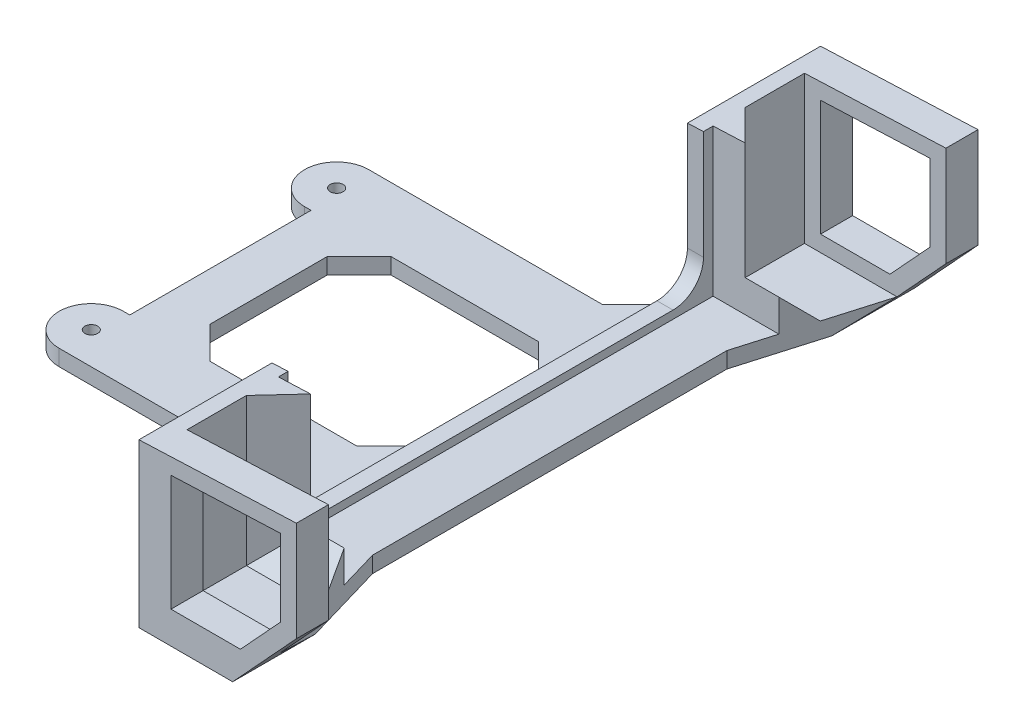
SolidWorks part; units mm, degrees
ref_plane "Front Plane" through (0, 0, 0) normal (0, 0, 1) x (1, 0, 0)
ref_plane "Top Plane" through (0, 0, 0) normal (0, 1, 0) x (1, 0, 0)
ref_plane "Right Plane" through (0, 0, 0) normal (1, 0, 0) x (0, 0, -1)
sketch "Sketch2" plane through (0, 0, 0) normal (0, 0, 1) x (1, 0, 0)
  line L2 (-5, -50.9445) -> (-5, -0.2052)
  line L4 (0, 0) -> (0, -45.9445)
  line L8 (44.0837, -29.3894) -> (44.0837, 1.809)
  line L9 (-5, -50.9445) -> (24.2279, -50.9445)
  line L13 (28.8337, -45.9445) -> (0, -45.9445)
  line L14 (44.0837, -29.3894) -> (24.2279, -50.9445)
  line L15 (44.0837, 1.809) -> (-5, -0.2052)
  dimension "D1" = 45.9445
  dimension "D2" = 2.35
  dimension "D3" = 28.8337
  dimension "D4" = 15.25
  dimension "D5" = 45
  dimension "D8" = 5
  dimension "D9" = 5
extrude "Boss-Extrude1" add sketch "Sketch2" along normal blind 10 contours L9 L14 L8 L15 L2
extrude "Boss-Extrude6" add sketch "Sketch2<5>" against normal blind 41 contours L13 L9 region at (-4.3884, -25.5748, 0)
sketch "Sketch2<5>" plane through (0, 0, 0) normal (0, 0, 1) x (1, 0, 0) same geometry as "Sketch2"
sketch "Sketch6" plane through (0, 0, 0) normal (1, 0, 0) x (0, 0, -1)
  line L0 (41, 0) -> (41, -45.9445) construction
  line L1 (41, -45.9445) -> (0, -45.9445) construction
  line L5 (41, -16.7445) -> (33, -16.7445) construction
  line L6 (33, 0) -> (33, -16.7445) construction
  line L8 (31.5, 0) -> (31.5, -33.9445)
  line L9 (31.5, 0) -> (41, 0)
  line L10 (41, 0) -> (41, -24.4445)
  line L11 (41, 0) -> (0, 0) construction
  circle A0 centre (41, -33.9445) radius 8 construction
  arc A1 (31.5, -33.9445) -> (41, -24.4445) centre (41, -33.9445) ccw
  circle A2 centre (41, -33.9445) radius 9.5 construction
  point P13 (41, -25.9445)
  point P15 (29.7596, -19.9849)
  point P16 (31.5, -33.9445)
  point P19 (0, 0)
  point P22 (33, 0)
  point P23 (41, -24.4445)
  dimension "D2" = 16
  dimension "D1" = 12
  dimension "D4" = 9.2
  dimension "D5" = 8
  dimension "Margin" = 1.5
extrude "Cut-Extrude1" cut sketch "Sketch6" against normal up to next
sketch "Sketch7" plane through (0, 0, 0) normal (0, 0, -1) x (-1, 0, 0)
  line L5 (-5, -4.799) -> (-39.0837, -3.4004)
  line L6 (-5, -4.799) -> (-39.0837, -3.4004)
  line L7 (-39.0837, -27.4374) -> (-26.6415, -40.9445)
  line L8 (-39.0837, -27.4374) -> (-26.6415, -40.9445)
  line L11 (-26.6415, -40.9445) -> (-5, -40.9445)
  line L12 (-5, -40.9445) -> (-5, -4.799)
  line L14 (-39.0837, -3.4004) -> (-39.0837, -27.4374)
  line L17 (-5, -40.9445) -> (-5, -4.799)
  line L19 (-39.0837, -3.4004) -> (-39.0837, -27.4374)
  line L22 (-26.6415, -40.9445) -> (-5, -40.9445)
  dimension "D1" = 5
extrude "Cut-Extrude2" cut sketch "Sketch7" against normal up to next
ref_plane "Plane1" through (0, 0, -28.5) normal (0, 0, 1) x (1, 0, 0)
sketch "Sketch10" plane through (0, 0, -28.5) normal (0, 0, 1) x (1, 0, 0)
  line L0 (28.8337, -45.9445) -> (0, -45.9445) construction
  line L1 (28.8337, -45.9445) -> (0, -45.9445)
  line L2 (0, 0) -> (0, -45.9445) construction
  line L3 (0, 0) -> (0, -45.9445)
  line L4 (28.8337, -45.9445) -> (28.8337, -35.9445)
  line L5 (28.8337, -35.9445) -> (10, -35.9445)
  line L6 (10, -35.9445) -> (10, 0.4103)
  line L7 (0, 0) -> (10, 0.4103)
  line L9 (44.0837, 1.809) -> (0, 0) construction
  dimension "D1" = 10
  dimension "D2" = 10
extrude "Boss-Extrude9" add sketch "Sketch10" along normal blind 10
chamfer "Chamfer3" distance 10 angle 45 2 edges at (19.4169, -35.9445, -18.5) (10, -17.7671, -18.5)
sketch "Sketch11" plane through (0, -45.9445, 0) normal (0, 1, 0) x (1, 0, 0)
  line L0 (28.8337, 41) -> (16.8337, 41)
  line L1 (28.8337, 41) -> (0, 41) construction
  line L2 (16.8337, 41) -> (28.8337, 0)
  line L3 (28.8337, 0) -> (28.8337, 41)
  dimension "D1" = 12
extrude "Cut-Extrude3" cut sketch "Sketch11" against normal through all both and the other way through all
ref_plane "Plane2" through (0, 0, -96.25) normal (0, 0, -1) x (-1, 0, 0)
sketch "Sketch12" plane through (0, 0, -41) normal (0, 0, -1) x (-1, 0, 0)
  line L6 (0, -45.9445) -> (-16.8337, -45.9445)
  line L7 (-16.8337, -45.9445) -> (-16.8337, -50.9445)
  line L8 (-16.8337, -50.9445) -> (5, -50.9445)
  line L9 (5, -50.9445) -> (5, -43.4445)
  line L10 (5, -43.4445) -> (0, -43.4445)
  line L11 (0, -43.4445) -> (0, -45.9445)
  line L12 (0, -45.9445) -> (-16.8337, -45.9445)
  line L13 (-16.8337, -45.9445) -> (-16.8337, -50.9445)
  line L14 (-16.8337, -50.9445) -> (5, -50.9445)
  line L15 (5, -50.9445) -> (5, -43.4445)
  line L16 (5, -43.4445) -> (0, -43.4445)
  line L17 (0, -43.4445) -> (0, -45.9445)
  dimension "D1" = 0
extrude "Boss-Extrude10" add sketch "Sketch12" along normal up to surface (55.25 mm away) up to plane "Plane2"
sketch "Sketch13" plane through (-5, 0, 0) normal (-1, 0, 0) x (0, 0, 1)
  line L0 (10, -50.9445) -> (-96.25, -50.9445) construction
  line L1 (-68, -50.9445) -> (-48, -50.9445)
  line L2 (-68, -50.9445) -> (-68, -45.9445)
  line L3 (-68, -45.9445) -> (-48, -45.9445)
  line L4 (-48, -50.9445) -> (-48, -45.9445)
  line L5 (-58, -45.9445) -> (-58, -50.9445) construction
  line L6 (-96.25, 11.2707) -> (-96.25, -11.2707) construction
  dimension "D1" = 5
  dimension "D2" = 20
  dimension "D3" = 38.25
extrude "Boss-Extrude11" add sketch "Sketch13" along normal blind 92.85
sketch "Sketch14" plane through (0, -45.9445, 0) normal (0, 1, 0) x (1, 0, 0)
  line L0 (-5, 58) -> (-97.85, 58) construction
  line L1 (-5, 48) -> (-5, 68) construction
  line L2 (-97.85, 48) -> (-97.85, 68) construction
  circle A0 centre (-87.85, 58) radius 2
  point P8 (-83.9374, 64)
  dimension "D1" = 10
  dimension "D2" = 4
extrude "Cut-Extrude4" cut sketch "Sketch14" against normal up to next
sketch "Sketch15" plane through (0, 0, -68) normal (0, 0, -1) x (-1, 0, 0)
  line L0 (97.85, -45.9445) -> (5, -45.9445) construction
  line L1 (85.85, -50.9445) -> (70.85, -50.9445)
  line L2 (85.85, -50.9445) -> (85.85, -45.9445)
  line L3 (85.85, -45.9445) -> (70.85, -45.9445)
  line L4 (70.85, -50.9445) -> (70.85, -45.9445)
  line L5 (97.85, -45.9445) -> (97.85, -50.9445) construction
  line L6 (97.85, -50.9445) -> (5, -50.9445) construction
  point P7 (91.0886, -50.9445)
  dimension "D1" = 15
  dimension "D2" = 12
extrude "Boss-Extrude12" add sketch "Sketch15" along normal up to surface (28.25 mm away) up to plane "Plane2"
mirror "Mirror1" about plane through (0, 0, -96.25) normal (0, 0, -1) of bodies 116
fillet "Fillet1" radius 10 4 edges at (-97.85, -48.4445, -144.5) (-97.85, -48.4445, -48) (-97.85, -48.4445, -124.5) (-97.85, -48.4445, -68)
chamfer "Chamfer4" distance 10 angle 45 6 edges at (-70.85, -48.4445, -124.5) (-5, -48.4445, -144.5) (-5, -48.4445, -124.5) (-5, -48.4445, -68) (-5, -48.4445, -48) (-70.85, -48.4445, -68)
